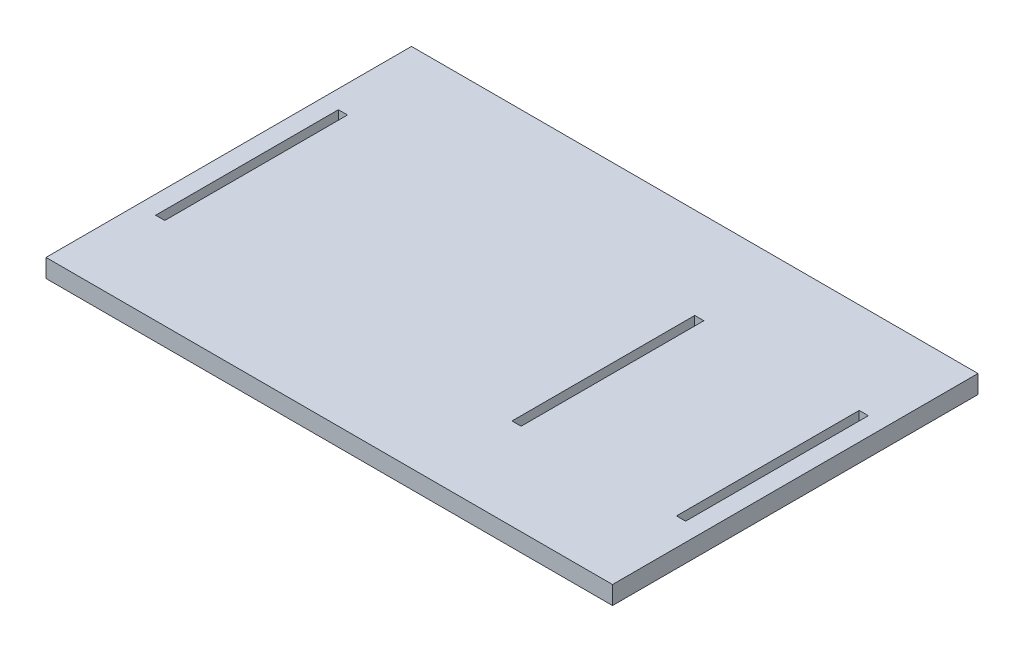
SolidWorks part; units mm, degrees
ref_plane "Alzado" through (0, 0, 0) normal (0, 0, 1) x (1, 0, 0)
ref_plane "Planta" through (0, 0, 0) normal (0, 1, 0) x (1, 0, 0)
ref_plane "Vista lateral" through (0, 0, 0) normal (1, 0, 0) x (0, 0, -1)
sketch "Croquis1" plane through (0, 0, 0) normal (0, 1, 0) x (1, 0, 0)
  line L0 (-155, 0) -> (155, 0) construction
  line L1 (-155, -100) -> (155, -100)
  line L2 (-155, -100) -> (-155, 100)
  line L3 (-155, 100) -> (155, 100)
  line L4 (155, -100) -> (155, 100)
  line L5 (-155, -100) -> (155, 100) construction
  line L6 (-155, 100) -> (155, -100) construction
  line L7 (145, -50) -> (145, 50)
  line L8 (-145, -50) -> (-140, -50)
  line L9 (-145, -50) -> (-145, 50)
  line L10 (-145, 50) -> (-140, 50)
  line L11 (-140, -50) -> (-140, 50)
  line L12 (-145, -50) -> (-140, 50) construction
  line L13 (-145, 50) -> (-140, -50) construction
  line L14 (50, -50) -> (55, -50)
  line L15 (50, -50) -> (50, 50)
  line L16 (50, 50) -> (55, 50)
  line L17 (55, -50) -> (55, 50)
  line L18 (50, -50) -> (55, 50) construction
  line L19 (50, 50) -> (55, -50) construction
  line L20 (140, -50) -> (145, -50)
  line L21 (140, -50) -> (140, 50)
  line L22 (140, 50) -> (145, 50)
  point P0 (0, 0)
  point P8 (-142.5, 0)
  point P13 (52.5, 0)
  dimension "D1" = 200
  dimension "D2" = 310
  dimension "D3" = 100
  dimension "D4" = 10
  dimension "D5" = 5
  dimension "D6" = 5
  dimension "D7" = 100
  dimension "D9" = 10
  dimension "D8" = 2
extrude "Saliente-Extruir1" add sketch "Croquis1" along normal blind 10
